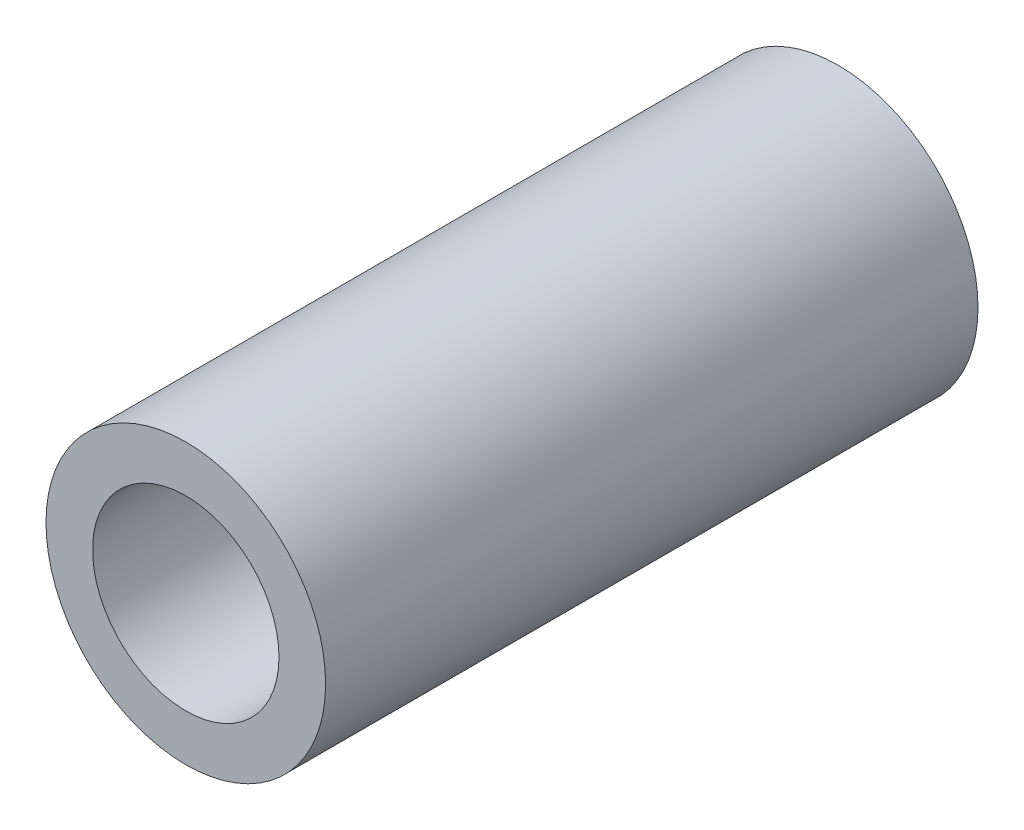
SolidWorks part; units mm, degrees
ref_plane "Plan de face" through (0, 0, 0) normal (1, 0, 0) x (0, 1, 0)
ref_plane "Plan de dessus" through (0, 0, 0) normal (0, 0, 1) x (0, 1, 0)
ref_plane "Plan de droite" through (0, 0, 0) normal (0, 1, 0) x (-1, 0, 0)
sketch "Esquisse1" plane through (0, 0, 0) normal (0, 0, 1) x (0, 1, 0)
  circle A0 centre (0, 0) radius 7.5
  dimension "D1" = 15
extrude "Boss.-Extru.1" add sketch "Esquisse1" along normal blind 35
sketch "Esquisse2" plane through (0, 0, 35) normal (0, 0, 1) x (1, 0, 0)
  circle A0 centre (0, 0) radius 5
  dimension "D1" = 10
extrude "Enlèv. mat.-Extru.1" cut sketch "Esquisse2" against normal blind 16
sketch "Esquisse3" plane through (0, 0, 0) normal (0, 0, -1) x (1, 0, 0)
  circle A0 centre (0, 0) radius 4.1
  dimension "D1" = 8.2
extrude "Enlèv. mat.-Extru.2" cut sketch "Esquisse3" against normal blind 16
sketch "Esquisse5" plane through (0, 0, 16) normal (0, 0, -1) x (1, 0, 0)
  line L0 (-2.8569, 2.9408) -> (3.2938, 2.4415)
  arc A0 (-2.8569, 2.9408) -> (3.2938, 2.4415) centre (0, 0) cw
  circle A1 centre (0, 0) radius 4.1 construction
  dimension "D1" = 2.7
extrude "Boss.-Extru.3" add sketch "Esquisse5" along normal blind 9
